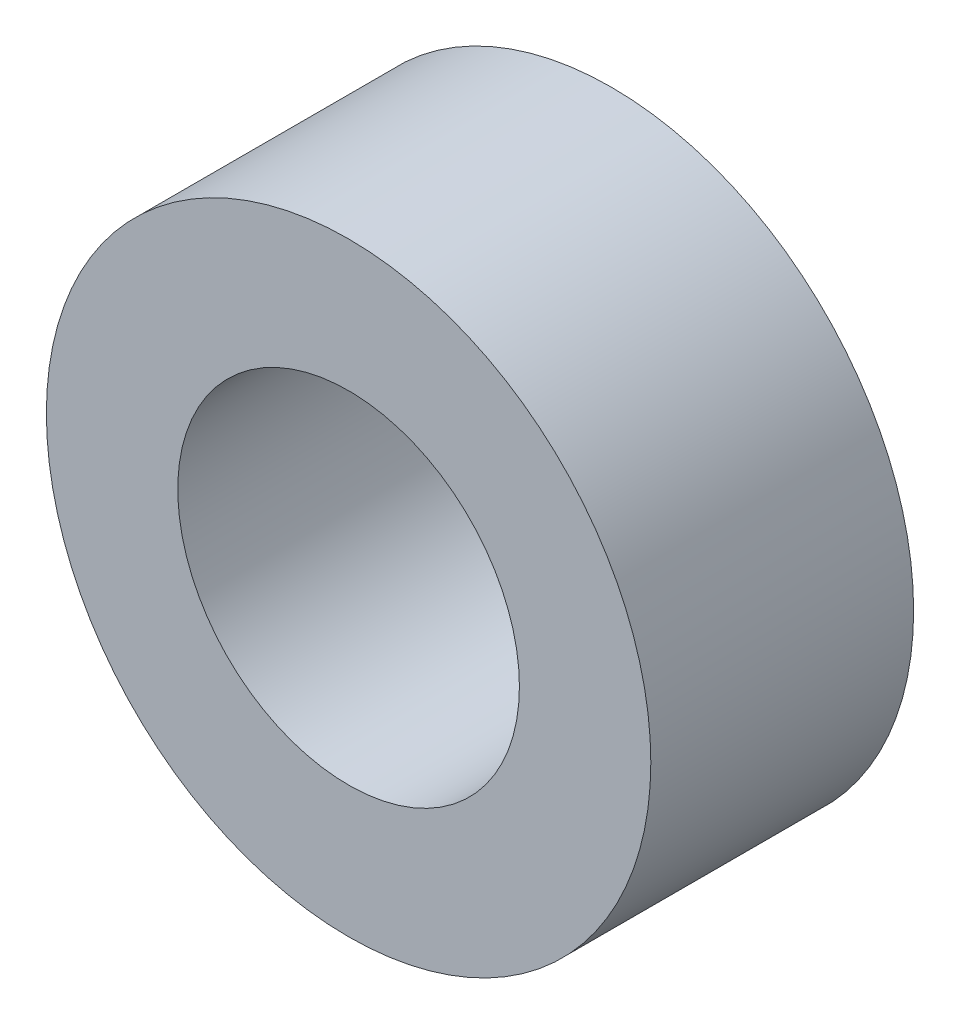
SolidWorks part; units mm, degrees
ref_plane "Front Plane" through (0, 0, 0) normal (0, 0, 1) x (1, 0, 0)
ref_plane "Top Plane" through (0, 0, 0) normal (0, 1, 0) x (1, 0, 0)
ref_plane "Right Plane" through (0, 0, 0) normal (1, 0, 0) x (0, 0, -1)
sketch "Sketch1" plane through (0, 0, 0) normal (0, 0, 1) x (1, 0, 0)
  circle A0 centre (0, 0) radius 2.875
  circle A1 centre (0, 0) radius 1.625
  dimension "D1" = 5.75
  dimension "D2" = 3.25
extrude "Boss-Extrude1" add sketch "Sketch1" along normal blind 2.5
